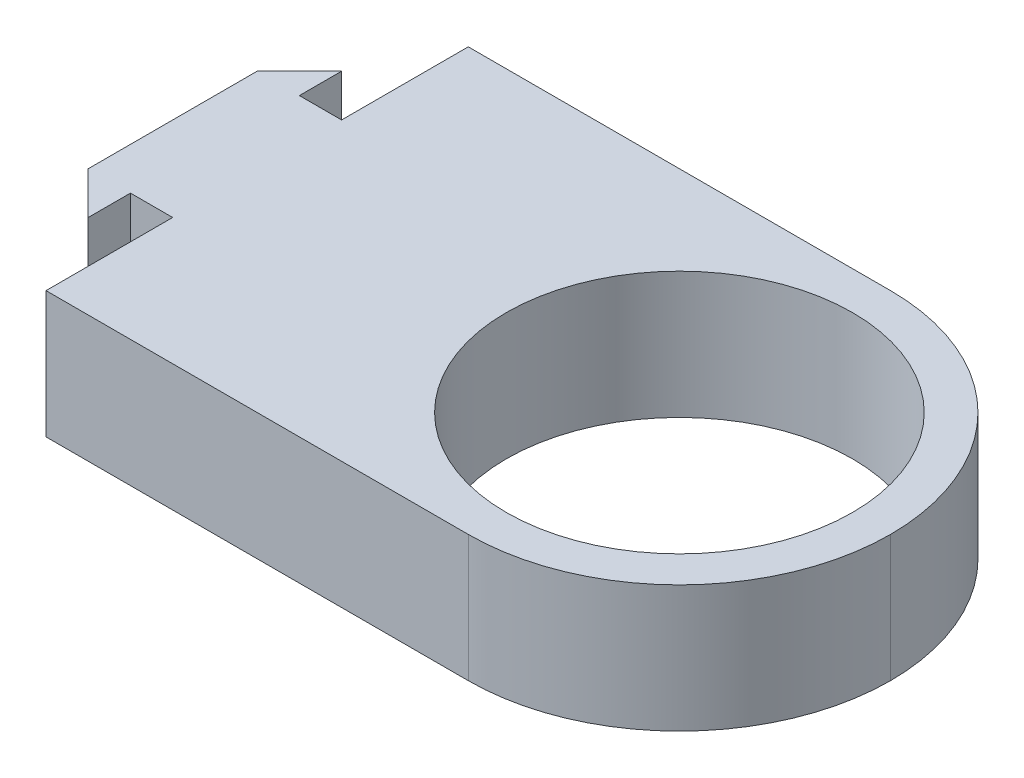
SolidWorks part; units mm, degrees
ref_plane "Plano frontal" through (0, 0, 0) normal (0, 0, 1) x (1, 0, 0)
ref_plane "Plano superior" through (0, 0, 0) normal (0, 1, 0) x (1, 0, 0)
ref_plane "Plano direito" through (0, 0, 0) normal (1, 0, 0) x (0, 0, -1)
sketch "Esboço1" plane through (0, 0, 0) normal (0, 1, 0) x (1, 0, 0)
  line L1 (-15, 10) -> (15, 10)
  line L2 (-15, 10) -> (-15, -10)
  line L3 (-15, -10) -> (15, -10)
  line L4 (15, 10) -> (15, -10)
  line L5 (-15, 10) -> (15, -10) construction
  line L6 (-15, -10) -> (15, 10) construction
  point P0 (0, 0)
  dimension "D1" = 20
  dimension "D2" = 30
extrude "Ressalto-extrusão1" add sketch "Esboço1" along normal mid plane 6
sketch "Esboço2" plane through (0, 3, 0) normal (0, 1, 0) x (1, 0, 0)
  line L0 (-15, 0) -> (15, 0) construction
  line L1 (-15, 10) -> (-15, -10) construction
  line L2 (15, -10) -> (15, 10) construction
  line L3 (0, 10) -> (0, -10) construction
  line L4 (15, 10) -> (-15, 10) construction
  line L5 (-15, -10) -> (15, -10) construction
  circle A0 centre (5, 0) radius 8.2
  dimension "D1" = 16.4
  dimension "D2" = 20
extrude "Corte-extrusão1" cut sketch "Esboço2" against normal through all
fillet "Filete1" radius 10 2 edges at (15, 0, -10) (15, 0, 10)
sketch "Esboço3" plane through (-15, 0, 0) normal (-1, 0, 0) x (0, 0, 1)
  line L0 (-10, -3) -> (10, -3) construction
  line L1 (-4, 3) -> (4, 3)
  line L2 (-4, 3) -> (-4, -3)
  line L3 (-4, -3) -> (4, -3)
  line L4 (4, 3) -> (4, -3)
  line L5 (-4, 3) -> (4, -3) construction
  line L6 (-4, -3) -> (4, 3) construction
  point P0 (0, 0)
  dimension "D1" = 8
extrude "Ressalto-extrusão2" add sketch "Esboço3" along normal blind 2
sketch "Esboço4" plane through (-17, 0, 0) normal (-1, 0, 0) x (0, 0, 1)
  line L0 (-10, 3) -> (-4, 3) construction
  line L1 (-6, 3) -> (6, 3)
  line L2 (-6, 3) -> (-6, -3)
  line L3 (-6, -3) -> (6, -3)
  line L4 (6, 3) -> (6, -3)
  line L5 (-6, 3) -> (6, -3) construction
  line L6 (-6, -3) -> (6, 3) construction
  point P0 (0, 0)
  dimension "D1" = 12
extrude "Ressalto-extrusão3" add sketch "Esboço4" along normal blind 2
chamfer "Chanfro1" distance 2 angle 45 2 edges at (-19, 0, 6) (-19, 0, -6)
